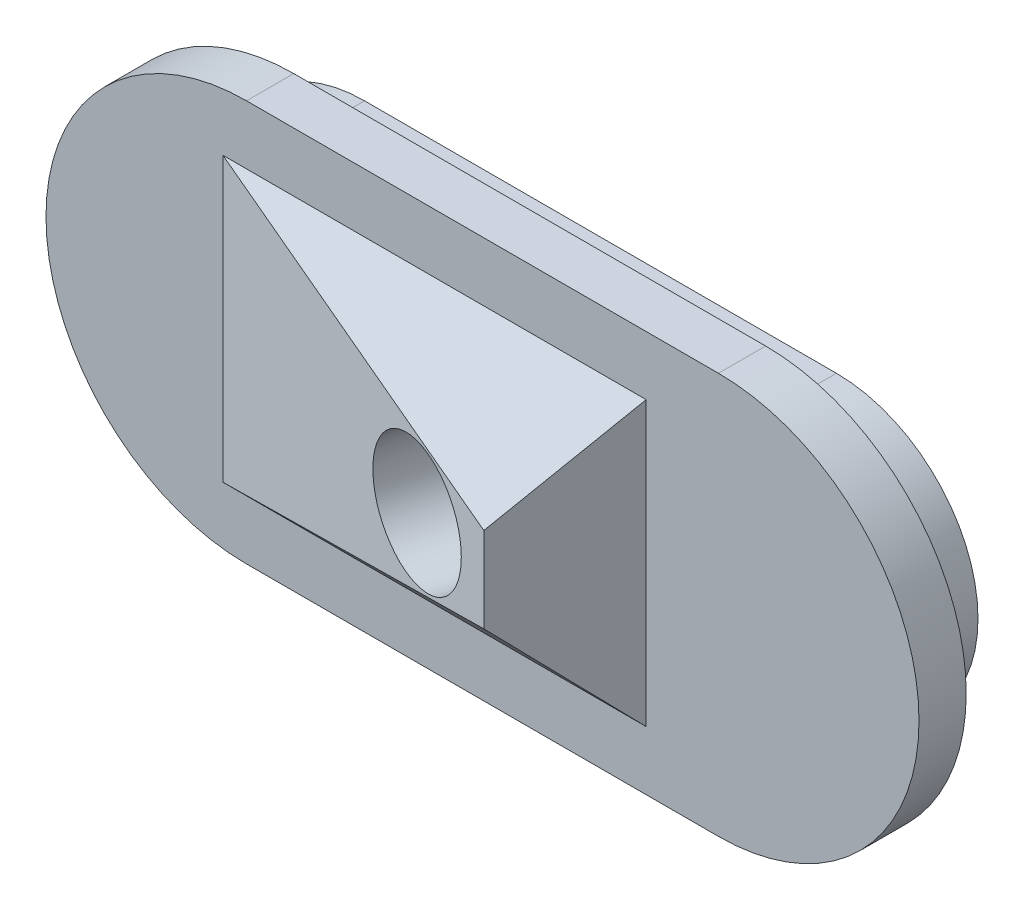
SolidWorks part; units mm, degrees
ref_plane "Front Plane" through (0, 0, 0) normal (0, 0, 1) x (1, 0, 0)
ref_plane "Top Plane" through (0, 0, 0) normal (0, 1, 0) x (1, 0, 0)
ref_plane "Right Plane" through (0, 0, 0) normal (1, 0, 0) x (0, 0, -1)
sketch "Sketch2" plane through (0, 0, 0) normal (0, 0, 1) x (1, 0, 0)
  line L0 (-10, 0) -> (10, 0) construction
  line L1 (55, 0) -> (-55, 0) construction
  line L2 (-10, 6) -> (10, 6)
  line L3 (-10, -6) -> (10, -6)
  arc A0 (-10, 6) -> (-10, -6) centre (-10, 0) ccw
  arc A1 (10, -6) -> (10, 6) centre (10, 0) ccw
  point P5 (0, 0)
  dimension "D1" = 12
  dimension "D2" = 20
extrude "Boss-Extrude1" add sketch "Sketch2" along normal mid plane 10
sketch "Sketch3" plane through (0, 0, 0) normal (0, 1, 0) x (1, 0, 0)
  line L0 (-5, 5) -> (-5, 9.8231)
  line L1 (10, 5) -> (-10, 5) construction
  line L2 (-5, 9.8231) -> (13, 5)
  line L3 (13, 5) -> (-5, 5)
  line L4 (-11, -5) -> (7, -9.8231)
  line L6 (7, -9.8231) -> (7, -5)
  line L7 (7, -5) -> (-11, -5)
  line L8 (0, -44.7868) -> (0, 44.7868) construction
  line L9 (-16, -5) -> (-10, -5) construction
  dimension "D1" = 15
  dimension "D2" = 15
  dimension "D3" = 18
  dimension "D4" = 5
  dimension "D5" = 18
  dimension "D6" = 7
extrude "Boss-Extrude2" add sketch "Sketch3" along normal up to surface and the other way up to surface up to face at (0, 6, 0) other way up to face at (0, -6, 0)
sketch "Sketch8" plane through (0, 0, 5) normal (0, 0, 1) x (1, 0, 0)
  line L0 (-10, 0) -> (10, 0) construction
  line L1 (55, 0) -> (-55, 0) construction
  line L2 (-10, 8.5) -> (10, 8.5)
  line L3 (-10, -8.5) -> (10, -8.5)
  arc A0 (-10, 8.5) -> (-10, -8.5) centre (-10, 0) ccw
  arc A1 (10, -8.5) -> (10, 8.5) centre (10, 0) ccw
  point P5 (0, 0)
  dimension "D1" = 17
  dimension "D2" = 20
extrude "Boss-Extrude3" add sketch "Sketch8" against normal blind 2
mirror "Mirror1" about plane through (0, 0, 0) normal (0, 0, 1) of "Boss-Extrude3"
sketch "Sketch4" plane through (-1.9869, 0, 7.4151) normal (-0.2588, 0, 0.9659) x (0.9659, 0, 0.2588)
  line L0 (55, 0) -> (-55, 0) construction
  line L1 (9.3039, 6) -> (9.3039, -6) construction
  circle A0 centre (2.3039, 0) radius 2.65
  dimension "D1" = 5.3
  dimension "D2" = 7
extrude "Cut-Extrude1" cut sketch "Sketch4" against normal through all
sketch "Sketch9" plane through (0, 0, 0) normal (0, 1, 0) x (1, 0, 0)
  line L0 (-44.2539, 0) -> (44.2539, 0) construction
  line L1 (-32.1911, 0) -> (32.6746, 0)
  line L2 (-32.1911, 0) -> (-32.1911, 28.9569)
  line L3 (-32.1911, 28.9569) -> (32.6746, 28.9569)
  line L4 (32.6746, 0) -> (32.6746, 28.9569)
extrude "Cut-Extrude2" cut sketch "Sketch9" against normal mid plane 65
sketch "Sketch10" plane through (7, 0, 0) normal (1, 0, 0) x (0, 0, -1)
  line L0 (-5, 6) -> (-9.8231, 1)
  line L1 (-9.8231, 6) -> (-9.8231, -6) construction
  line L2 (-9.8231, 1) -> (-9.8231, -1)
  line L3 (-9.8231, -1) -> (-5, -6)
  line L4 (-5, -6) -> (-15.1617, -6)
  line L5 (-15.1617, -6) -> (-15.1617, 6)
  line L6 (-15.1617, 6) -> (-5, 6)
  dimension "D1" = 5.3386
  dimension "D2" = 5
  dimension "D3" = 5
extrude "Cut-Extrude3" cut sketch "Sketch10" against normal through all
chamfer "Chamfer3" distance 3 angle 70 1 edges at (7, 0, 9.8231) first distance on face at (2.7982, 0, 8.6972)
